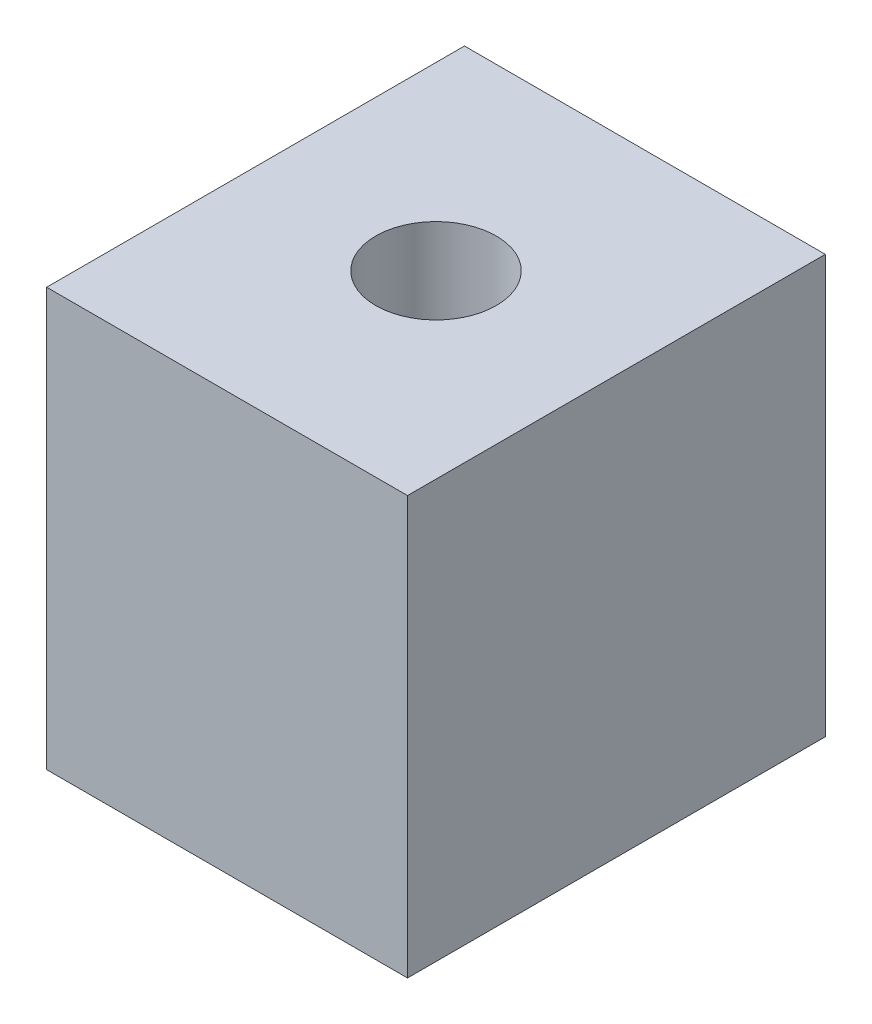
SolidWorks part; units mm, degrees
ref_plane "Front Plane" through (0, 0, 0) normal (0, 0, 1) x (1, 0, 0)
ref_plane "Top Plane" through (0, 0, 0) normal (0, 1, 0) x (1, 0, 0)
ref_plane "Right Plane" through (0, 0, 0) normal (1, 0, 0) x (0, 0, -1)
sketch "Sketch1" plane through (0, 0, 0) normal (0, 1, 0) x (1, 0, 0)
  line L1 (-9.5, -11) -> (9.5, -11)
  line L2 (-9.5, -11) -> (-9.5, 11)
  line L3 (-9.5, 11) -> (9.5, 11)
  line L4 (9.5, -11) -> (9.5, 11)
  line L5 (-9.5, -11) -> (9.5, 11) construction
  line L6 (-9.5, 11) -> (9.5, -11) construction
  point P0 (0, 0)
  dimension "D1" = 19
  dimension "D2" = 22
extrude "Boss-Extrude1" add sketch "Sketch1" against normal blind 22
sketch "Sketch2" plane through (0, 0, 0) normal (0, 1, 0) x (1, 0, 0)
  circle A0 centre (0, 0) radius 3.175
  dimension "D1" = 6.35
extrude "Cut-Extrude1" cut sketch "Sketch2" against normal up to surface (22 mm away) up to face at (0, -22, 0)
